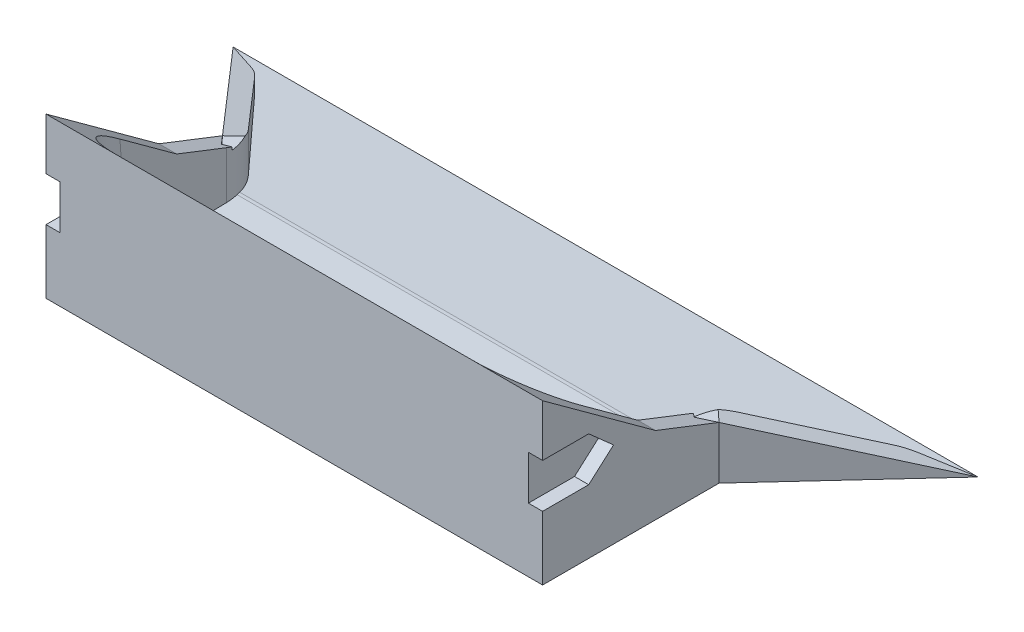
SolidWorks part; units mm, degrees
ref_plane "Front Plane" through (0, 0, 0) normal (0, 0, 1) x (1, 0, 0)
ref_plane "Top Plane" through (0, 0, 0) normal (0, 1, 0) x (1, 0, 0)
ref_plane "Right Plane" through (0, 0, 0) normal (1, 0, 0) x (0, 0, -1)
sketch "Sketch4" plane through (0, 0, 0) normal (0, 1, 0) x (1, 0, 0)
  line L0 (0, 49.75) -> (-34.9965, 87.75)
  line L1 (0, 0) -> (140, 0)
  line L2 (0, 0) -> (0, 49.75)
  line L4 (140, 0) -> (140, 49.75)
  line L5 (-34.9965, 87.75) -> (174.9965, 87.75)
  line L6 (174.9965, 87.75) -> (140, 49.75)
  dimension "D1" = 49.75
  dimension "D2" = 38
  dimension "D3" = 140
  dimension "D4" = 51.66
extrude "Boss-Extrude3" add sketch "Sketch4" along normal blind 45
sketch "Sketch5" plane through (140, 0, 0) normal (1, 0, 0) x (0, 0, -1)
  line L0 (0, 45) -> (3, 2)
  line L1 (3, 2) -> (49.75, 3)
  line L3 (49.75, 3) -> (87.75, 0)
  line L4 (0, 45) -> (87.75, 45)
  line L5 (87.75, 45) -> (87.75, 0)
  line L6 (0, 45) -> (0, 0) construction
  line L7 (0, 0) -> (49.75, 0) construction
  line L9 (49.75, 45) -> (49.75, 0) construction
  dimension "D1" = 3
  dimension "D2" = 2
  dimension "D3" = 3
extrude "Cut-Extrude1" cut sketch "Sketch5" against normal through all both and the other way through all
sketch "Sketch6" plane through (140, 0, 0) normal (1, 0, 0) x (0, 0, -1)
  line L0 (0, 45) -> (31.8543, 21.8098)
  line L1 (31.8543, 21.8098) -> (87.75, 0)
  line L2 (49.75, 3) -> (49.75, 14.8272)
  line L3 (49.75, 3) -> (87.75, 0)
  line L4 (0, 45) -> (49.75, 45)
  line L5 (49.75, 45) -> (49.75, 14.8272)
  dimension "D1" = 35
  dimension "D2" = 60
sketch "Sketch12" plane through (0, 0, 0) normal (0, -1, 0) x (1, 0, 0)
  line L0 (135, 0) -> (135, -51.7016)
  line L1 (135, -51.7016) -> (161.7382, -80.7345)
  line L2 (0, 0) -> (140, 0) construction
  line L3 (140, -49.75) -> (140, -3) construction
  line L4 (174.9965, -87.75) -> (140, -49.75) construction
  line L5 (140, -49.75) -> (174.9965, -87.75) construction
  line L9 (161.7382, -80.7345) -> (174.9965, -87.75)
  line L16 (0, 0) -> (0, -49.75)
  line L17 (0, -49.75) -> (-34.9965, -87.75)
  line L18 (-34.9965, -87.75) -> (174.9965, -87.75)
  line L19 (174.9965, -87.75) -> (140, -49.75)
  line L20 (140, -49.75) -> (140, 0)
  line L21 (140, 0) -> (0, 0)
  line L22 (0, 0) -> (0, -49.75)
  line L23 (0, -49.75) -> (-34.9965, -87.75)
  line L24 (-34.9965, -87.75) -> (174.9965, -87.75)
  line L27 (140, 0) -> (0, 0)
  line M6 (174.9965, -87.75) -> (140, -49.75)
  line M7 (140, -49.75) -> (140, 0)
  line M8 (140, 0) -> (0, 0)
  dimension "D1" = 5
  dimension "D2" = 5
  dimension "D4" = 15
  dimension "D5" = 0
extrude "Boss-Extrude10" add sketch "Sketch12" against normal blind 45 contours L1 L9 L0 M6 M7 M8 region at (137.5, 0, -0.9644)
extrude "Cut-Extrude2" cut sketch "Sketch6" against normal through all both and the other way through all contours L5 L4 L0 L1 region at (140, 34.0635, -32.4884)
sketch "Sketch13" plane through (50.9597, 0, 46.9319) normal (0.7356, 0, 0.6774) x (0.6774, 0, -0.7356)
  line L0 (131.4365, 14.8272) -> (183.0965, 0)
  line L1 (131.4365, 14.8272) -> (131.4365, 45)
  line L2 (131.4365, 45) -> (183.0965, 45)
  line L3 (183.0965, 45) -> (183.0965, 0)
extrude "Cut-Extrude3" cut sketch "Sketch13" against normal through all both and the other way through all
sketch "Sketch14" plane through (89.0403, 0, -96.6819) normal (0.6774, 0, -0.7356) x (-0.7356, 0, -0.6774)
  line L0 (-69.2784, 45) -> (-64.2784, 45)
  line L1 (-64.2784, 45) -> (-64.2784, 14.8272)
  line L2 (-64.2784, 14.8272) -> (-69.2784, 14.8272)
  line L3 (-69.2784, 14.8272) -> (-69.2784, 45)
  line M5 (-64.2784, 14.8272) -> (-64.2784, 45)
  line M6 (-64.2784, 45) -> (-69.2784, 45)
  line M7 (-69.2784, 45) -> (-69.2784, 14.8272)
  line M8 (-69.2784, 14.8272) -> (-64.2784, 14.8272)
extrude "Cut-Extrude4" cut sketch "Sketch14" against normal blind 5 contours M8 M5 M6 M7 region at (138.1611, 29.9136, -51.4436)
ref_plane "Plane2" through (70, 0, 0) normal (1, 0, 0) x (0, 0, -1)
mirror "Mirror1" about plane through (70, 0, 0) normal (1, 0, 0) of "Cut-Extrude4", "Cut-Extrude3", "Cut-Extrude2", "Boss-Extrude10"
fillet "Fillet2" radius 15 7 edges at (5, 23.5, -1.5) (135, 23.5, -1.5) (-21.7382, 2.3064, -80.7345) (5, 8.8365, -51.7016) (161.7382, 2.3064, -80.7345) (135, 8.8365, -51.7016) (70, 2, -3)
fillet "Fillet4" radius 10 1 edges at (70, 3, -49.75)
sketch "Sketch16" plane through (140, 0, 0) normal (1, 0, 0) x (0, 0, -1)
  line L0 (0, 15) -> (49.75, 15) construction
  line L1 (0, 45) -> (0, 0) construction
  line L2 (49.75, 14.8272) -> (49.75, 0) construction
  line L3 (0, 0) -> (49.75, 0) construction
  line L4 (0, 18) -> (13, 18)
  line L5 (0, 30.42) -> (13, 30.42)
  line L6 (13, 30.42) -> (20, 24.21)
  line L7 (20, 24.21) -> (13, 18)
  line L9 (0, 45) -> (0, 30.42)
  line L14 (49.75, 0) -> (49.75, 14.8272)
  line L15 (49.75, 14.8272) -> (31.8543, 21.8098)
  line L17 (0, 45) -> (0, 0)
  line L18 (0, 0) -> (49.75, 0)
  line L19 (49.75, 0) -> (49.75, 14.8272)
  line L22 (0, 18) -> (0, 0)
  line L23 (0, 0) -> (49.75, 0)
  line L24 (49.75, 14.8272) -> (31.8543, 21.8098)
  line L25 (31.8543, 21.8098) -> (0, 45)
  line L27 (31.8543, 21.8098) -> (0, 45)
  line M14 (0, 45) -> (0, 0)
  dimension "D1" = 15
  dimension "D2" = 3
  dimension "D3" = 12.42
  dimension "D4" = 20
  dimension "D5" = 13
  dimension "D6" = 0
extrude "Cut-Extrude5" cut sketch "Sketch16" against normal blind 4 contours L7 L6 L5 L4 M14 region at (140, 24.21, -8.3737)
mirror "Mirror2" about plane through (70, 0, 0) normal (1, 0, 0) of "Cut-Extrude5"
